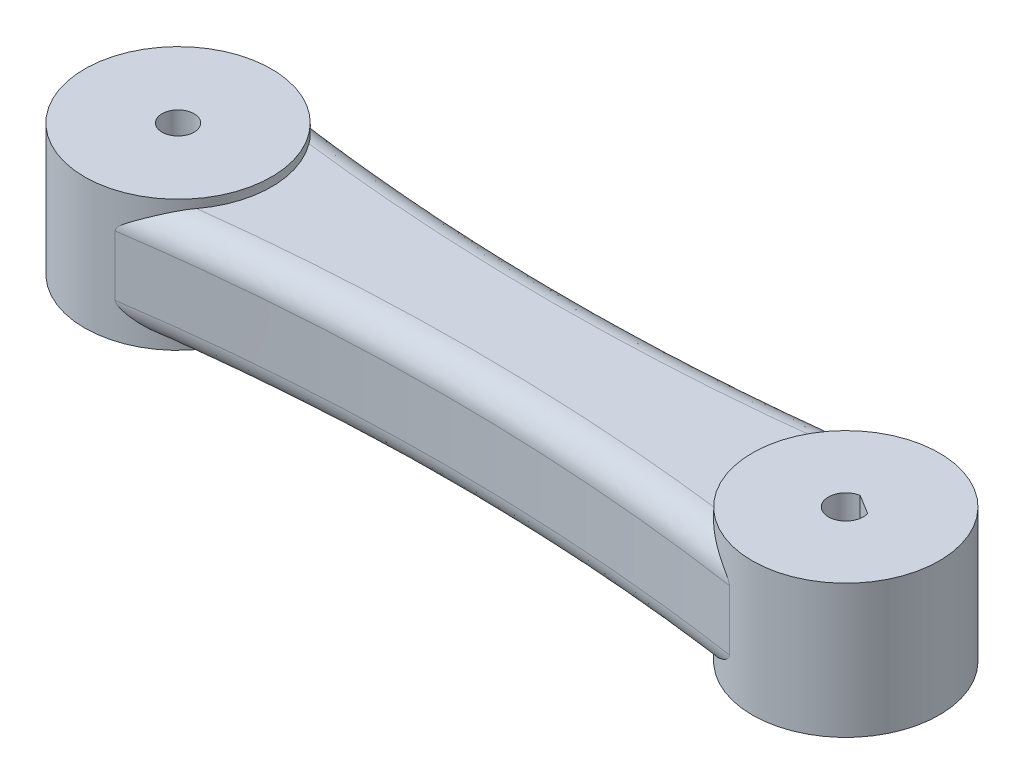
SolidWorks part; units mm, degrees
ref_plane "Front Plane" through (0, 0, 0) normal (0, 0, 1) x (1, 0, 0)
ref_plane "Top Plane" through (0, 0, 0) normal (0, 1, 0) x (1, 0, 0)
ref_plane "Right Plane" through (0, 0, 0) normal (1, 0, 0) x (0, 0, -1)
sketch "Sketch5" plane through (0, 0, 0) normal (0, 1, 0) x (1, 0, 0)
  line L0 (195.0422, -100.8243) -> (695.0422, -100.8243) construction
  line L1 (445.0422, -100.8243) -> (445.0422, -321.5033) construction
  line L2 (215.0422, -33.7422) -> (215.0422, -167.9063) construction
  line L3 (195.0422, -100.8243) -> (195.0422, 49.0469) construction
  line L4 (675.0422, -33.7422) -> (675.0422, -167.9063) construction
  circle A0 centre (195.0422, -100.8243) radius 70
  circle A1 centre (695.0422, -100.8243) radius 70
  spline S0 degree 2 poles (215.0422, -167.9063) (445.0422, -134.0715) (675.0422, -167.9063) knots 0 0 0 1 1 1
  spline S1 degree 2 poles (215.0422, -33.7422) (445.0422, -67.577) (675.0422, -33.7422) knots 0 0 0 1 1 1
  dimension "D2" = 140
  dimension "D1" = 500
  dimension "D3" = 20
extrude "Boss-Extrude3" add sketch "Sketch5" along normal mid plane 85 contours S1 A0 S0 A1 region at (445.0422, 0, 100.8243)
extrude "Boss-Extrude4" add sketch "Sketch5<3>" along normal mid plane 98 contours A0 region at (195.0422, 0, 100.8243)
sketch "Sketch5<3>" plane through (0, 0, 0) normal (0, 1, 0) x (1, 0, 0) same geometry as "Sketch5"
extrude "Boss-Extrude11" add sketch "Sketch5<6>" along normal mid plane 100 contours A1 region at (695.0422, 0, 100.8243)
sketch "Sketch5<6>" plane through (0, 0, 0) normal (0, 1, 0) x (1, 0, 0) same geometry as "Sketch5"
fillet "Fillet5" radius 20 4 edges
sketch "Sketch6" plane through (0, -50, 0) normal (0, 1, 0) x (1, 0, 0)
  circle A0 centre (195.0422, -100.8243) radius 12
  dimension "D1" = 24
extrude "Cut-Extrude1" cut sketch "Sketch6" along normal blind 112
sketch "Sketch8" plane through (0, 0, 0) normal (0, 1, 0) x (1, 0, 0)
  point P3 (195.0422, -100.8243)
sketch "Sketch10" plane through (0, -50, 0) normal (0, -1, 0) x (1, 0, 0)
  line L0 (707.4318, 96.8873) -> (692.9782, 87.9892)
  arc A0 (707.4318, 96.8873) -> (692.9782, 87.9892) centre (695.0422, 100.8243) ccw
extrude "Cut-Extrude2" cut sketch "Sketch10" against normal blind 151
